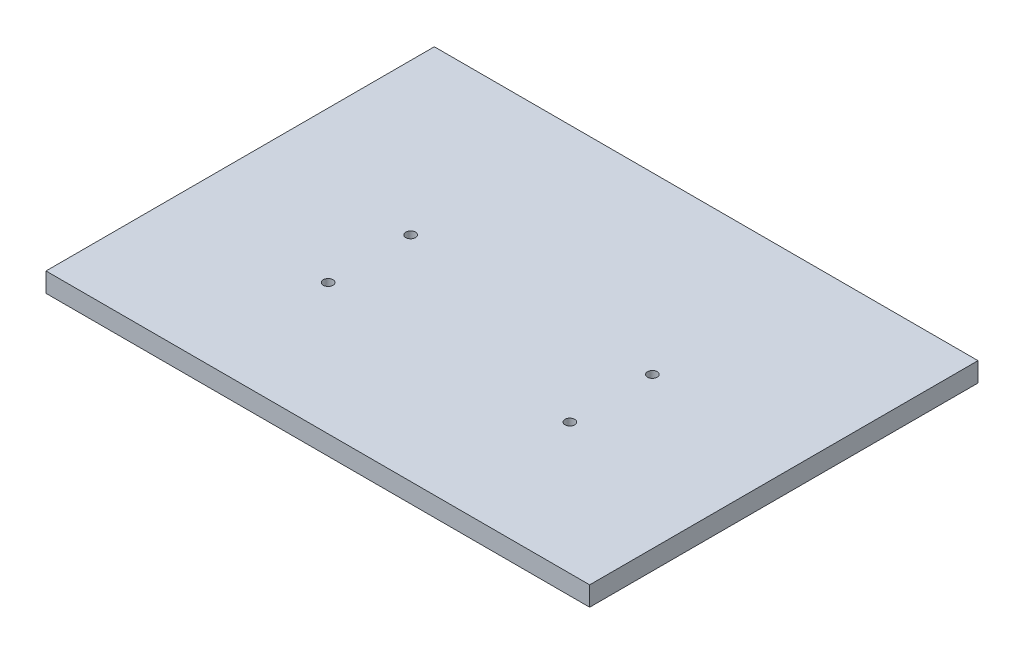
SolidWorks part; units mm, degrees
material "Alloy Steel (SS)"
ref_plane "Front Plane" through (0, 0, 0) normal (0, 0, 1) x (1, 0, 0)
ref_plane "Top Plane" through (0, 0, 0) normal (0, 1, 0) x (1, 0, 0)
ref_plane "Right Plane" through (0, 0, 0) normal (1, 0, 0) x (0, 0, -1)
sketch "Sketch1" plane through (0, 0, 0) normal (0, 1, 0) x (1, 0, 0)
  line L1 (-175.7216, 120.2519) -> (535.4784, 120.2519)
  line L2 (-175.7216, 120.2519) -> (-175.7216, -387.7481)
  line L3 (-175.7216, -387.7481) -> (535.4784, -387.7481)
  line L4 (535.4784, 120.2519) -> (535.4784, -387.7481)
  dimension "D1" = 711.2
  dimension "D2" = 508
  dimension "D3" = 535.4784
  dimension "D4" = 120.2519
extrude "Boss-Extrude1" add sketch "Sketch1" along normal blind 25.4
sketch "Sketch3" plane through (0, 25.4, 0) normal (0, 1, 0) x (1, 0, 0)
  line L1 (-175.7216, -387.7481) -> (535.4784, -387.7481) construction
  line L2 (-175.7216, 120.2519) -> (-175.7216, -387.7481) construction
  circle A2 centre (21.8904, -216.2981) radius 6.35
  circle A3 centre (21.8904, -108.3481) radius 6.35
  circle A4 centre (338.1204, -108.3481) radius 6.35
  circle A5 centre (338.1204, -216.2981) radius 6.35
  dimension "D4" = 12.7
  dimension "D5" = 12.7
  dimension "D6" = 12.7
  dimension "D7" = 12.7
  dimension "D8" = 171.45
  dimension "D2" = 197.612
  dimension "D3" = 513.842
  dimension "D9" = 316.23
  dimension "D11" = 107.95
extrude "Cut-Extrude1" cut sketch "Sketch3" against normal through all
